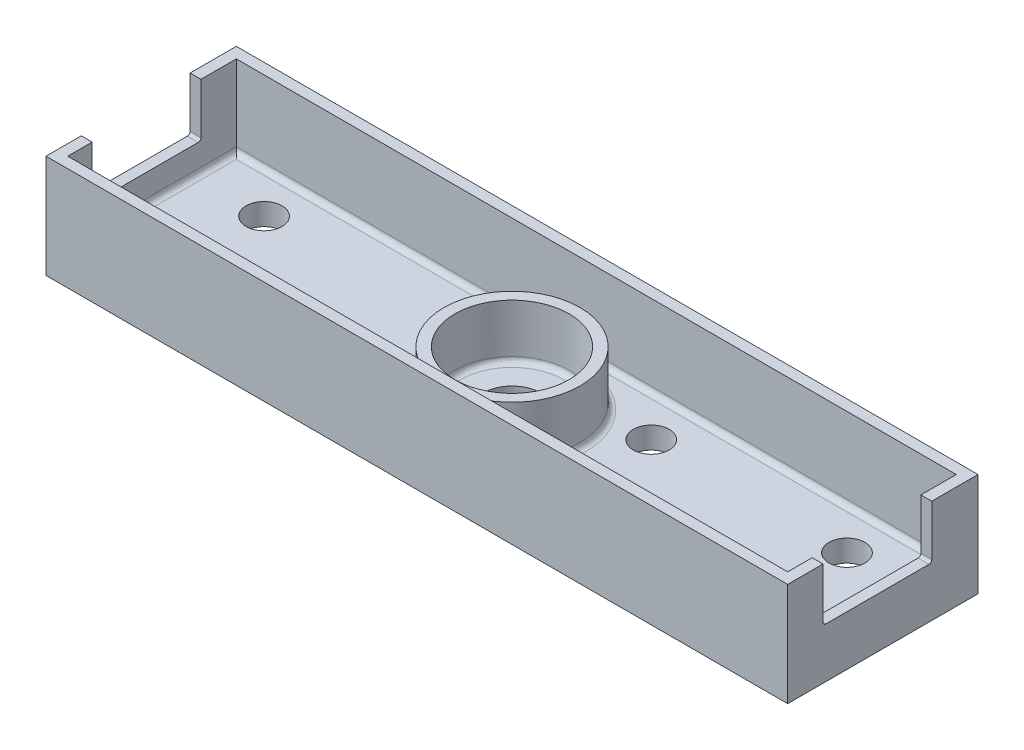
SolidWorks part; units mm, degrees
material "Nylon 6/10"
ref_plane "Front Plane" through (0, 0, 0) normal (0, 0, 1) x (1, 0, 0)
ref_plane "Top Plane" through (0, 0, 0) normal (0, 1, 0) x (1, 0, 0)
ref_plane "Right Plane" through (0, 0, 0) normal (1, 0, 0) x (0, 0, -1)
sketch "Sketch1" plane through (0, 0, 0) normal (0, 1, 0) x (1, 0, 0)
  line L1 (-34.1, -8.75) -> (0, -8.75)
  line L2 (-34.1, -8.75) -> (-34.1, 8.75)
  line L3 (-34.1, 8.75) -> (0, 8.75)
  line L4 (0, -8.75) -> (0, 8.75)
  line L5 (-34.1, -8.75) -> (0, 8.75) construction
  line L6 (-34.1, 8.75) -> (0, -8.75) construction
  point P0 (-17.05, 0)
  point P8 (0, 0)
  dimension "D1" = 34.1
  dimension "D2" = 17.5
extrude "Boss-Extrude1" add sketch "Sketch1" along normal blind 9.5
shell "Shell1" thickness 1 removed face at (-17.05, 9.5, 0) removed face at (0, 4.75, 0)
sketch "Sketch2" plane through (0, 0, 0) normal (0, -1, 0) x (1, 0, 0)
  line L0 (-8.8, 4) -> (-26.8, 4) construction
  line L1 (-17.8, 4) -> (-17.8, 0) construction
  line L2 (-8.8, 4) -> (-8.8, -4) construction
  line L3 (-8.8, -4) -> (-26.8, -4) construction
  line L4 (-26.8, -4) -> (-26.8, 4) construction
  line L5 (-8.8, 0) -> (-17.8, 0) construction
  line L6 (-17.05, -8.75) -> (-17.05, 8.75) construction
  line L8 (-8.8, 0) -> (0, 0) construction
  line L9 (0, -8.75) -> (-34.1, -8.75) construction
  line L10 (-34.1, 8.75) -> (0, 8.75) construction
  circle A0 centre (-8.8, 4) radius 1.65
  circle A1 centre (-26.8, 4) radius 1.65
  circle A2 centre (-8.8, -4) radius 1.65
  circle A3 centre (-26.8, -4) radius 1.65
  circle A4 centre (-17.8, 0) radius 2.625 construction
  circle A5 centre (-8.8, 4) radius 2.5 construction
  circle A6 centre (-8.8, -4) radius 2.5 construction
  circle A7 centre (-26.8, -4) radius 2.5 construction
  circle A8 centre (-26.8, 4) radius 2.5 construction
  dimension "D1" = 3.3
  dimension "D4" = 5.25
  dimension "D5" = 5
  dimension "D2" = 18
  dimension "D3" = 8
  dimension "D6" = 0.75
extrude "Cut-Extrude1" cut sketch "Sketch2" against normal through all
sketch "Sketch3" plane through (0, 2, 0) normal (0, 1, 0) x (1, 0, 0)
  line L1 (-2.9573, -5.1559) -> (2.9865, -5.139)
  line L2 (2.9865, -5.139) -> (5.9438, 0.0169)
  line L3 (5.9438, 0.0169) -> (2.9573, 5.1559)
  line L4 (2.9573, 5.1559) -> (-2.9865, 5.139)
  line L5 (-2.9865, 5.139) -> (-5.9438, -0.0169)
  line L6 (-5.9438, -0.0169) -> (-2.9573, -5.1559)
  circle A0 centre (0, 0) radius 2.6 construction
  circle A1 centre (0, 0) radius 5.1475 construction
  dimension "D1" = 5.2
extrude "Cut-Extrude2" [suppressed] cut sketch "Sketch3" against normal blind 0.5
sketch "Sketch4" plane through (-34.1, 0, 0) normal (-1, 0, 0) x (0, 0, 1)
  line L0 (-8.75, 9.5) -> (8.75, 9.5) construction
  line L1 (-4.5, 9.5) -> (5.5, 9.5)
  line L2 (-4.5, 9.5) -> (-4.5, 4.6)
  line L3 (-4.5, 4.6) -> (5.5, 4.6)
  line L4 (5.5, 9.5) -> (5.5, 4.6)
  line L5 (0.5, 4.6) -> (0.5, 0) construction
  line L11 (-8.75, 0) -> (8.75, 0) construction
  dimension "D1" = 10
  dimension "D2" = 4.9
  dimension "D3" = 0.5
extrude "Cut-Extrude3" cut sketch "Sketch4" against normal up to next
mirror "Mirror1" about plane through (0, 0, 0) normal (1, 0, 0) of bodies 105
sketch "Sketch5" plane through (0, 2, 0) normal (0, 1, 0) x (1, 0, 0)
  circle A0 centre (0, 0) radius 2.65
  dimension "D1" = 5.3
extrude "Cut-Extrude4" cut sketch "Sketch5" against normal through all
sketch "Sketch6" plane through (0, 2, 0) normal (0, 1, 0) x (1, 0, 0)
  circle A0 centre (0, 0) radius 6.25
  circle A1 centre (0, 0) radius 5.25
  dimension "D1" = 10.5
  dimension "D2" = 1
extrude "Boss-Extrude2" add sketch "Sketch6" along normal blind 5
fillet "Fillet3" radius 0.25 4 edges at (-33.6, 4.6, 5.5) (-33.6, 4.6, -4.5) (33.6, 4.6, -4.5) (33.6, 4.6, 5.5)
fillet "Fillet4" radius 0.5 6 edges at (0, 2, -6.25) (0, 2, 5.25) (-33.1, 2, 0) (0, 2, -7.75) (33.1, 2, 0) (0, 2, 7.75)
